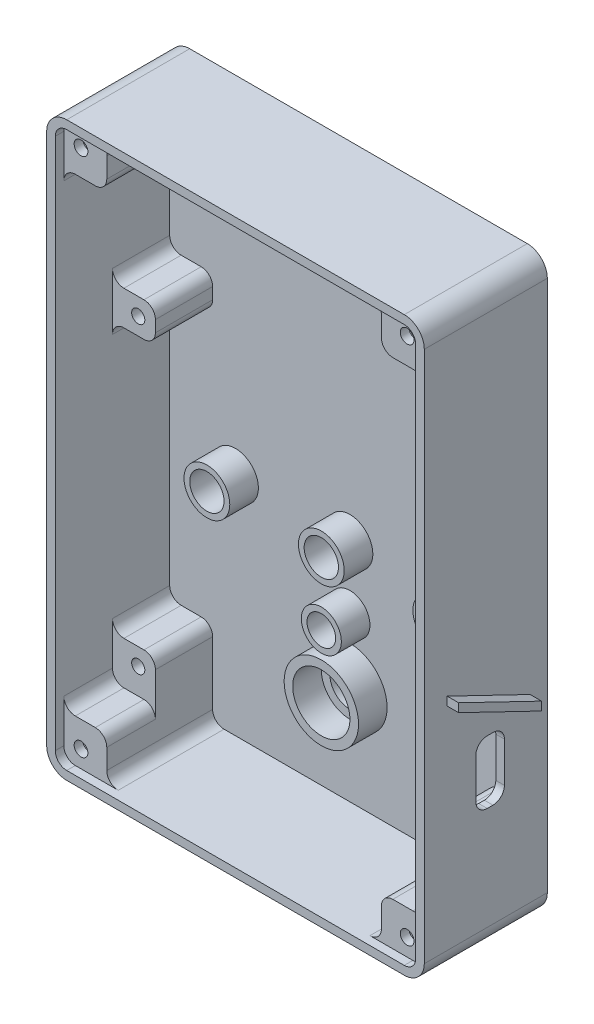
SolidWorks part; units mm, degrees
material "ABS"
ref_plane "Спереди" through (0, 0, 0) normal (0, 0, 1) x (1, 0, 0)
ref_plane "Сверху" through (0, 0, 0) normal (0, 1, 0) x (1, 0, 0)
ref_plane "Справа" through (0, 0, 0) normal (1, 0, 0) x (0, 0, -1)
sketch "Эскиз1" plane through (0, 0, 0) normal (0, 0, 1) x (1, 0, 0)
  line L1 (-33, -50) -> (33, -50)
  line L2 (-33, -50) -> (-33, 50)
  line L3 (-33, 50) -> (33, 50)
  line L4 (33, -50) -> (33, 50)
  line L5 (-33, -50) -> (33, 50) construction
  line L6 (-33, 50) -> (33, -50) construction
  line L7 (-31.5, -48.5) -> (31.5, -48.5)
  line L8 (-31.5, -48.5) -> (-31.5, 48.5)
  line L9 (-31.5, 48.5) -> (31.5, 48.5)
  line L10 (31.5, -48.5) -> (31.5, 48.5)
  line L11 (-31.5, -48.5) -> (31.5, 48.5) construction
  line L12 (-31.5, 48.5) -> (31.5, -48.5) construction
  point P0 (0, 0)
  point P6 (0, 0)
  dimension "D1" = 66
  dimension "D2" = 100
  dimension "D3" = 1.5
  dimension "D4" = 1.5
extrude "Бобышка-Вытянуть1" add sketch "Эскиз1" along normal blind 20
sketch "Эскиз3" plane through (0, 0, 0) normal (0, 0, -1) x (-1, 0, 0)
  line L1 (-33, 50) -> (33, 50)
  line L2 (-33, 50) -> (-33, -50)
  line L3 (-33, -50) -> (33, -50)
  line L4 (33, 50) -> (33, -50)
extrude "Бобышка-Вытянуть2" add sketch "Эскиз3" along normal blind 1.5
sketch "Эскиз4" plane through (0, 0, 0) normal (0, 0, 1) x (1, 0, 0)
  line L0 (-31.5, 48.5) -> (-31.5, -48.5) construction
  line L1 (-31.5, 19.5) -> (-24, 19.5)
  line L2 (-31.5, 19.5) -> (-31.5, 13.5)
  line L3 (-31.5, 13.5) -> (-24, 13.5)
  line L4 (-24, 19.5) -> (-24, 13.5)
  line L5 (31.5, -48.5) -> (31.5, 48.5) construction
  line L6 (31.5, 19.5) -> (24, 19.5)
  line L7 (31.5, 19.5) -> (31.5, 13.5)
  line L8 (31.5, 13.5) -> (24, 13.5)
  line L9 (24, 19.5) -> (24, 13.5)
  line L10 (-31.5, -48.5) -> (31.5, -48.5) construction
  line L11 (-31.5, -41) -> (-24, -41)
  line L12 (-31.5, -41) -> (-31.5, -33.5)
  line L13 (-31.5, -33.5) -> (-24, -33.5)
  line L14 (-24, -41) -> (-24, -33.5)
  line L15 (31.5, -41) -> (24, -41)
  line L16 (31.5, -41) -> (31.5, -33.5)
  line L17 (31.5, -33.5) -> (24, -33.5)
  line L18 (24, -41) -> (24, -33.5)
  line L19 (31.5, -48.5) -> (31.5, 48.5) construction
  dimension "D1" = 7.5
  dimension "D2" = 7.5
  dimension "D3" = 6
  dimension "D4" = 47
  dimension "D5" = 7.5
extrude "Бобышка-Вытянуть3" add sketch "Эскиз4" along normal blind 10
sketch "Эскиз5" plane through (0, 0, 10) normal (0, 0, 1) x (1, 0, 0)
  line L0 (-24, 13.5) -> (-24, 19.5) construction
  line L1 (24, 19.5) -> (24, 13.5) construction
  line L2 (-31.5, 13.5) -> (-24, 13.5) construction
  line L3 (-24, -33.5) -> (-31.5, -33.5) construction
  point P0 (-27, 16.5)
  point P1 (27, 16.5)
  point P2 (27, -36.5)
  point P3 (-27, -36.5)
  dimension "D1" = 3
  dimension "D2" = 3
  dimension "D3" = 3
  dimension "D4" = 3
hole_wizard "Сверло под метчик  спиральное M2.21" positions "Эскиз6" profile "Эскиз7" hole size "M2.2x0.45" standard "DIN"
sketch "Эскиз6" plane through (0, 0, 10) normal (0, 0, 1) x (1, 0, 0)
  point P0 (-27, 16.5)
  point P3 (27, 16.5)
  point P6 (27, -36.5)
  point P9 (-27, -36.5)
sketch "Эскиз7" plane through (-27, 16.5, 10) normal (1, 0, 0) x (0, -1, 0)
  line L0 (0, 0) -> (0, 4.691)
  line L1 (0, 4.691) -> (1.15, 4)
  line L2 (1.15, 4) -> (1.15, 0)
  line L5 (1.15, 0) -> (0, 0)
  line L10 (0, 4.691) -> (-1.15, 4) construction
  line L11 (0, -6.35) -> (0, 107.95) construction
  dimension "Диаметр отверстия" = 2.3
  dimension "Глубина отверстия" = 4
  dimension "Угол заточки сверла" = 118
sketch "Эскиз8" plane through (0, 0, 0) normal (0, 0, 1) x (1, 0, 0)
  line L0 (-24, -41) -> (-24, -33.5) construction
  line L1 (-31.5, 48.5) -> (-24, 48.5)
  line L2 (-31.5, 48.5) -> (-31.5, 41)
  line L3 (-31.5, 41) -> (-24, 41)
  line L4 (-24, 48.5) -> (-24, 41)
  line L5 (31.5, 48.5) -> (24, 48.5)
  line L6 (31.5, 48.5) -> (31.5, 41)
  line L7 (31.5, 41) -> (24, 41)
  line L8 (24, 48.5) -> (24, 41)
  line L9 (31.5, -48.5) -> (24, -48.5)
  line L10 (31.5, -48.5) -> (31.5, -41)
  line L11 (31.5, -41) -> (24, -41)
  line L12 (24, -48.5) -> (24, -41)
  line L13 (-31.5, -48.5) -> (-24, -48.5)
  line L14 (-31.5, -48.5) -> (-31.5, -41)
  line L15 (-31.5, -41) -> (-24, -41)
  line L16 (-24, -48.5) -> (-24, -41)
  line L18 (24, -33.5) -> (24, -41) construction
  line L19 (-24, 19.5) -> (-31.5, 19.5) construction
  line L21 (-31.5, -41) -> (-24, -41) construction
extrude "Бобышка-Вытянуть4" add sketch "Эскиз8" along normal blind 18.5
fillet "Скругление1" radius 2 20 edges at (-31.5, -33.5, 5) (-24, -33.5, 5) (-24, -48.5, 9.25) (24, -48.5, 9.25) (24, -33.5, 5) (31.5, -33.5, 5) (31.5, 13.5, 5) (24, 13.5, 5) (24, 19.5, 5) (31.5, 19.5, 5) (-31.5, 13.5, 5) (-24, 13.5, 5) (-24, 19.5, 5) (-31.5, 19.5, 5) (-31.5, 41, 9.25) (-24, 41, 9.25) (-24, 48.5, 9.25) (31.5, 41, 9.25) (24, 48.5, 9.25) (24, 41, 9.25)
fillet "Скругление3" radius 2 8 edges at (-31.5, -48.5, 19.25) (-31.5, -41, 14.25) (-24, -41, 14.25) (31.5, -48.5, 19.25) (24, -41, 14.25) (31.5, -41, 14.25) (-31.5, 48.5, 19.25) (31.5, 48.5, 19.25)
fillet "Скругление4" radius 3.5 4 edges at (-33, -50, 9.25) (33, -50, 9.25) (33, 50, 9.25) (-33, 50, 9.25)
sketch "Эскиз9" plane through (0, 0, 0) normal (0, 0, 1) x (1, 0, 0)
  line L0 (-29.5, -50) -> (29.5, -50) construction
  circle A0 centre (-20, -9) radius 3
  circle A1 centre (20, -9) radius 3
  circle A2 centre (0, -20) radius 2.5
  circle A3 centre (0, -9) radius 3
  circle A4 centre (0, -31) radius 3.5
  dimension "D1" = 6
  dimension "D6" = 7
  dimension "D8" = 5
  dimension "D2" = 11
  dimension "D3" = 11
  dimension "D4" = 20
  dimension "D5" = 20
  dimension "D7" = 19
extrude "Вырез-Вытянуть1" cut sketch "Эскиз9" against normal through all
sketch "Эскиз10" plane through (0, 0, 0) normal (0, 0, 1) x (1, 0, 0)
  circle A0 centre (-20, -9) radius 3
  circle A1 centre (0, -20) radius 2.5 construction
  circle A2 centre (0, -9) radius 3
  circle A3 centre (20, -9) radius 3
  circle A4 centre (0, -20) radius 2.5
  circle A5 centre (-20, -9) radius 3 construction
  circle A6 centre (0, -9) radius 4
  circle A7 centre (20, -9) radius 4
  circle A8 centre (0, -20) radius 3.5
  circle A9 centre (-20, -9) radius 4
  dimension "D1" = 1
  dimension "D2" = 1
extrude "Бобышка-Вытянуть5" add sketch "Эскиз10" along normal blind 5
sketch "Эскиз11" plane through (0, 0, -1.5) normal (0, 0, -1) x (-1, 0, 0)
  line L0 (29.5, 50) -> (-29.5, 50) construction
  line L1 (33, -46.5) -> (33, 46.5) construction
  line L2 (-29.5, -50) -> (29.5, -50) construction
  line L3 (-33, 46.5) -> (-33, -46.5) construction
  circle A0 centre (-28.5, 45.5) radius 2.5
  circle A1 centre (28.5, 45.5) radius 2.5
  circle A2 centre (28.5, -45.5) radius 2.5
  circle A3 centre (-28.5, -45.5) radius 2.5
  dimension "D2" = 5
  dimension "D1" = 4.5
  dimension "D3" = 4.5
  dimension "D4" = 4.5
  dimension "D5" = 4.5
extrude "Вырез-Вытянуть2" cut sketch "Эскиз11" against normal blind 18.5
sketch "Эскиз12" plane through (0, 0, 17) normal (0, 0, -1) x (-1, 0, 0)
  point P0 (-28.5, 45.5)
  point P1 (28.5, 45.5)
  point P3 (28.5, -45.5)
  point P5 (-28.5, -45.5)
hole_wizard "Отверстие с зазором M21" positions "Эскиз13" profile "Эскиз14" hole size "M2" standard "DIN" end condition through all
sketch "Эскиз13" plane through (0, 0, 17) normal (0, 0, -1) x (-1, 0, 0)
  point P0 (-28.5, 45.5)
  point P3 (28.5, 45.5)
  point P6 (28.5, -45.5)
  point P9 (-28.5, -45.5)
sketch "Эскиз14" plane through (28.5, 45.5, 17) normal (1, 0, 0) x (0, 1, 0)
  line L0 (0, 0) -> (0, 3)
  line L1 (0, 3) -> (1.2, 3)
  line L2 (1.2, 3) -> (1.2, 0)
  line L5 (1.2, 0) -> (0, 0)
  line L11 (0, -6.35) -> (0, 107.95) construction
  dimension "Диаметр сквозного отверстия" = 2.4
  dimension "Глубина сквозного отверстия" = 3
sketch "Эскиз15" plane through (31.5, 0, 0) normal (-1, 0, 0) x (0, 0, 1)
  line L1 (6, -28.5) -> (11, -28.5)
  line L2 (6, -28.5) -> (6, -17.5)
  line L3 (6, -17.5) -> (11, -17.5)
  line L4 (11, -28.5) -> (11, -17.5)
  line L5 (10, -39) -> (10, -31.5) construction
  dimension "D1" = 5
  dimension "D2" = 11
  dimension "D3" = 8
  dimension "D4" = 1
extrude "Вырез-Вытянуть3" cut sketch "Эскиз15" against normal through all
fillet "Скругление5" radius 2 4 edges at (32.25, -28.5, 11) (32.25, -17.5, 11) (32.25, -17.5, 6) (32.25, -28.5, 6)
sketch "Эскиз16" plane through (0, 0, 0) normal (0, 0, 1) x (1, 0, 0)
  circle A0 centre (0, -31) radius 5
  circle A1 centre (0, -31) radius 6.5
  dimension "D1" = 1.5
  dimension "D2" = 10
extrude "Бобышка-Вытянуть6" add sketch "Эскиз16" along normal blind 5
sketch "Эскиз19" plane through (33, 0, 0) normal (1, 0, 0) x (0, 0, -1)
  line L8 (-11, -19.5) -> (-11, -26.5)
  line L9 (-9, -28.5) -> (-8, -28.5)
  line L10 (-6, -26.5) -> (-6, -19.5)
  line L11 (-8, -17.5) -> (-9, -17.5)
  line L12 (-11, -19.5) -> (-11, -26.5)
  line L13 (-9, -28.5) -> (-8, -28.5)
  line L14 (-6, -26.5) -> (-6, -19.5)
  line L15 (-8, -17.5) -> (-9, -17.5)
  line L24 (-4.5, -26.5) -> (-4.5, -19.5)
  line L25 (-9, -30) -> (-8, -30)
  line L26 (-12.5, -19.5) -> (-12.5, -26.5)
  line L27 (-8, -16) -> (-9, -16)
  line L28 (-4.5, -26.5) -> (-4.5, -19.5)
  line L29 (-9, -30) -> (-8, -30)
  line L30 (-12.5, -19.5) -> (-12.5, -26.5)
  line L31 (-8, -16) -> (-9, -16)
  arc A8 (-11, -26.5) -> (-9, -28.5) centre (-9, -26.5) ccw
  arc A9 (-8, -28.5) -> (-6, -26.5) centre (-8, -26.5) ccw
  arc A10 (-6, -19.5) -> (-8, -17.5) centre (-8, -19.5) ccw
  arc A11 (-9, -17.5) -> (-11, -19.5) centre (-9, -19.5) ccw
  arc A12 (-11, -26.5) -> (-9, -28.5) centre (-9, -26.5) ccw
  arc A13 (-8, -28.5) -> (-6, -26.5) centre (-8, -26.5) ccw
  arc A14 (-6, -19.5) -> (-8, -17.5) centre (-8, -19.5) ccw
  arc A15 (-9, -17.5) -> (-11, -19.5) centre (-9, -19.5) ccw
  arc A20 (-4.5, -19.5) -> (-8, -16) centre (-8, -19.5) ccw
  arc A21 (-8, -30) -> (-4.5, -26.5) centre (-8, -26.5) ccw
  arc A22 (-12.5, -26.5) -> (-9, -30) centre (-9, -26.5) ccw
  arc A23 (-9, -16) -> (-12.5, -19.5) centre (-9, -19.5) ccw
  arc A24 (-4.5, -19.5) -> (-8, -16) centre (-8, -19.5) ccw
  arc A25 (-8, -30) -> (-4.5, -26.5) centre (-8, -26.5) ccw
  arc A26 (-12.5, -26.5) -> (-9, -30) centre (-9, -26.5) ccw
  arc A27 (-9, -16) -> (-12.5, -19.5) centre (-9, -19.5) ccw
  dimension "D1" = 1.5
  dimension "D2" = 0
extrude "Бобышка-Вытянуть7" [suppressed] add sketch "Эскиз19" along normal blind 2
sketch "Эскиз20" plane through (33, 0, 0) normal (1, 0, 0) x (0, 0, -1)
  line L0 (-16, -9.5) -> (-16, -8)
  line L1 (-16, -8) -> (-1.5, -15)
  line L2 (-1.5, -15) -> (-1.5, -16.5)
  line L3 (-1.5, -16.5) -> (-16, -9.5)
  line L4 (-20, -46.5) -> (-20, 46.5) construction
  line L5 (1.5, 46.5) -> (1.5, -46.5) construction
  line L7 (-9, -17.5) -> (-8, -17.5) construction
  dimension "D1" = 1.5
  dimension "D2" = 4
  dimension "D3" = 3
  dimension "D4" = 7
  dimension "D5" = 1
extrude "Бобышка-Вытянуть8" add sketch "Эскиз20" along normal blind 2
